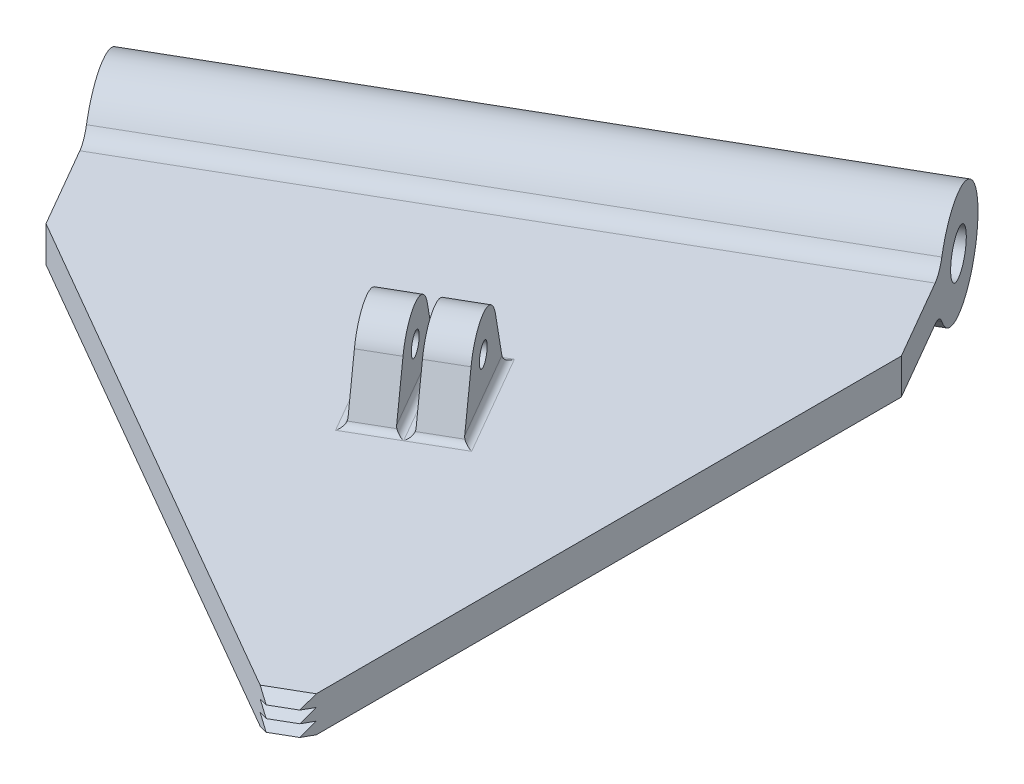
SolidWorks part; units mm, degrees
ref_plane "Front Plane" through (0, 0, 0) normal (0, 0, 1) x (1, 0, 0)
ref_plane "Top Plane" through (0, 0, 0) normal (0, 1, 0) x (1, 0, 0)
ref_plane "Right Plane" through (0, 0, 0) normal (1, 0, 0) x (0, 0, -1)
sketch "Sketch1" plane through (0, 0, 0) normal (0, 1, 0) x (1, 0, 0)
  line L0 (0, 87.9882) -> (0, 0)
  line L1 (0, 87.9882) -> (-76.2, 43.9941)
  line L2 (-76.2, 43.9941) -> (-76.2, -43.9941)
  line L3 (-76.2, -43.9941) -> (0, -87.9882)
  line L4 (0, -87.9882) -> (76.2, -43.9941)
  line L5 (76.2, -43.9941) -> (76.2, 43.9941)
  line L6 (76.2, 43.9941) -> (0, 87.9882)
  line L7 (0, 0) -> (-76.2, 43.9941)
  line L8 (-76.2, 43.9941) -> (-91.2, 69.9749)
  line L9 (-91.2, 69.9749) -> (-15, 113.9689)
  line L10 (-15, 113.9689) -> (0, 87.9882)
  circle A0 centre (0, 0) radius 76.2 construction
  circle A1 centre (0, 0) radius 12.7
  circle A2 centre (0, 0) radius 6.35
  dimension "D1" = 25.4
  dimension "D2" = 12.7
  dimension "D3" = 152.4
  dimension "D4" = 30
extrude "Boss-Extrude1" add sketch "Sketch1" along normal blind 5 contours A1 L0 L1 L7 | A2 L0 A1 L7 | L0 A2 L7 | L10 L9 L8 L1 region at (-25.9519, 0, -44.9501) region at (-45.6, 0, -78.9815) region at (-4.7163, 0, -8.1689) region at (-2.0213, 0, -3.5009)
sketch "Sketch2" plane through (-38.1, 0, 21.997) normal (-0.866, 0, 0.5) x (0.5, 0, 0.866)
  line L1 (-106.2, 5) -> (-106.2, 0) construction
  circle A0 centre (-99.1289, 2.5) radius 7.5
  point P9 (-106.2, 2.5)
  dimension "D1" = 15
extrude "Boss-Extrude2" add sketch "Sketch2" against normal up to surface (87.9882 mm away) up to face at (-7.5, 2.5, -100.9786)
sketch "Sketch3" plane through (-38.1, 0, 21.997) normal (-0.866, 0, 0.5) x (0.5, 0, 0.866)
  circle A0 centre (-99.1289, 2.5) radius 3
  circle A2 centre (-99.1289, 2.5) radius 7.5 construction
  dimension "D1" = 6
extrude "Cut-Extrude1" cut sketch "Sketch3" against normal up to surface (87.9882 mm away) up to face at (-5.7858, 2.5, -98.0096)
sketch "Sketch5" plane through (0, 5, 0) normal (0, 1, 0) x (1, 0, 0)
  line L0 (-6, 3.4641) -> (0, 6.9282)
  line L1 (0, 0) -> (-76.2, 43.9941) construction
  line L2 (0, 87.9882) -> (0, 0) construction
  line L7 (-84.1289, 57.7274) -> (-7.9289, 101.7215) construction
  line L13 (-7.9289, 101.7215) -> (-84.1289, 57.7274)
  line L14 (-84.1289, 57.7274) -> (-76.2, 43.9941)
  line L15 (-76.2, 43.9941) -> (0, 0)
  line L16 (0, 0) -> (0, 87.9882)
  line L17 (0, 87.9882) -> (-7.9289, 101.7215)
  line L20 (-6, 3.4641) -> (0, 0)
  line L21 (0, 0) -> (0, 6.9282)
  dimension "D1" = 6
  dimension "D2" = 0
extrude "Cut-Extrude2" cut sketch "Sketch5" against normal blind 5
ref_plane "Plane1" through (-3, 0, 1.7321) normal (0.866, 0, -0.5) x (0, 1, 0)
sketch "Sketch7" plane through (-3, 0, 1.7321) normal (0.866, 0, -0.5) x (0, 1, 0)
  line L0 (0, -6) -> (0.8333, -4)
  line L1 (0.8333, -4) -> (1.6667, -6)
  line L2 (0, -6) -> (5, -6) construction
  line L3 (1.6667, -6) -> (2.5, -4)
  line L4 (2.5, -4) -> (3.3333, -6)
  line L5 (3.3333, -6) -> (4.1667, -4)
  line L6 (4.1667, -4) -> (5, -6)
  line L7 (0.8333, -4) -> (4.1667, -4) construction
  line L8 (0, -6) -> (5, -6) construction
  line L9 (0, -6) -> (5, -6)
  dimension "D1" = 2
extrude "Boss-Extrude3" add sketch "Sketch7" along normal up to vertex (6.9282 mm away) contours L0 L9 L1 | L3 L9 L4 | L5 L9 L6 region at (-5.6667, 4.1667, -2.8868) region at (-5.6667, 2.5, -2.8868) region at (-5.6667, 0.8333, -2.8868) up to point (0, 5, -6.9282)
sketch "Sketch9" plane through (0, 0, 0) normal (-0.5, 0, 0.866) x (0.866, 0, 0.5)
  line L0 (0, 0) -> (0, 20)
  dimension "D1" = 20
sketch "Sketch10" plane through (0, 0, 0) normal (-0.5, 0, 0.866) x (0.866, 0, 0.5)
  line L0 (-6.9282, 5) -> (-87.9882, 5) construction
  line L1 (-92.9882, 0) -> (3.0718, 0)
  line L2 (-92.9882, 0) -> (-92.9882, 5)
  line L3 (-92.9882, 5) -> (3.0718, 5)
  line L4 (3.0718, 0) -> (3.0718, 5)
  line L5 (-6.9282, 1.6667) -> (-6.9282, 3.3333) construction
  line L6 (-87.9882, 5) -> (-87.9882, 0) construction
  line L7 (-6.9282, 0) -> (-87.9882, 0) construction
  dimension "D1" = 10
  dimension "D2" = 5
extrude "Cut-Extrude3" cut sketch "Sketch10" against normal blind 0.5 and the other way blind 10
ref_plane "Plane2" through (0, 0, 0) normal (0.866, 0, -0.5) x (-0.5, 0, -0.866)
mirror "Mirror1" about plane through (0, 0, 0) normal (0.866, 0, -0.5) of "Cut-Extrude3"
sketch "Sketch11" plane through (0, 0, 0) normal (0.866, 0, -0.5) x (-0.5, 0, -0.866)
  line L0 (53.8006, 12.7076) -> (51, 5)
  line L1 (6, 5) -> (77.2, 5) construction
  line L2 (63.1994, 12.7076) -> (66, 5)
  line L3 (66, 5) -> (51, 5)
  circle A0 centre (58.5, 11) radius 1.5
  arc A1 (63.1994, 12.7076) -> (53.8006, 12.7076) centre (58.5, 11) ccw
  dimension "D1" = 3
  dimension "D2" = 10
  dimension "D3" = 15
  dimension "D4" = 45
  dimension "D6" = 6
extrude "Boss-Extrude4" add sketch "Sketch11" along normal blind 5 from offset 1
mirror "Mirror2" about plane through (0, 0, 0) normal (0.866, 0, -0.5) of "Boss-Extrude4"
fillet "Fillet1" radius 1 8 edges at (-28.384, 5, -51.1625) (-30.116, 5, -50.1625) (-34.4462, 5, -47.6625) (-24.0538, 5, -53.6625) (-28.5311, 5, -42.4173) (-22.4689, 5, -45.9173) (-36.0311, 5, -55.4077) (-29.9689, 5, -58.9077)
fillet "Fillet2" radius 3 2 edges at (-46.0289, 0, -79.7244) (-46.0289, 5, -79.7244)
